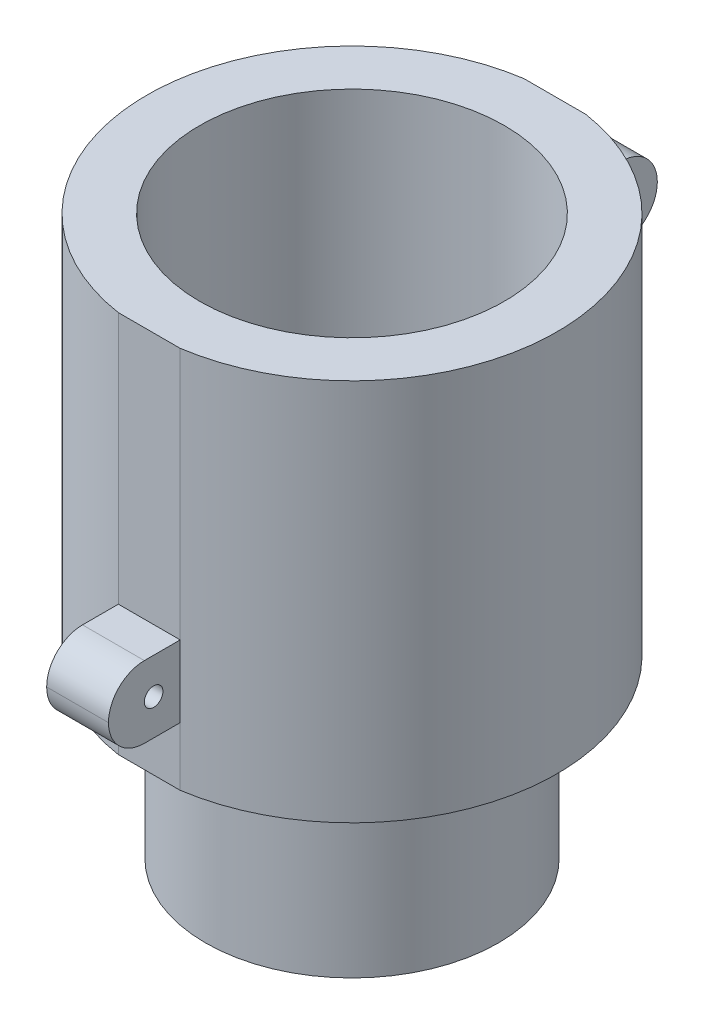
SolidWorks part; units mm, degrees
ref_plane "Front Plane" through (0, 0, 0) normal (0, 0, 1) x (1, 0, 0)
ref_plane "Top Plane" through (0, 0, 0) normal (0, 1, 0) x (1, 0, 0)
ref_plane "Right Plane" through (0, 0, 0) normal (1, 0, 0) x (0, 0, -1)
sketch "Sketch2" plane through (0, 0, 0) normal (0, 1, 0) x (1, 0, 0)
  circle A0 centre (0, 0) radius 17.5
  dimension "D1" = 35
extrude "Boss-Extrude1" add sketch "Sketch2" along normal blind 32.665
sketch "Sketch3" plane through (0, 0, 0) normal (0, -1, 0) x (1, 0, 0)
  circle A0 centre (0, 0) radius 12.5
extrude "Boss-Extrude2" add sketch "Sketch3" along normal blind 15
sketch "Sketch4" plane through (0, 32.665, 0) normal (0, 1, 0) x (1, 0, 0)
  circle A0 centre (0, 0) radius 13
extrude "Cut-Extrude1" cut sketch "Sketch4" against normal blind 25
sketch "Sketch8" plane through (0, 32.665, 0) normal (0, 1, 0) x (1, 0, 0)
  line L1 (-17.5, 0) -> (17.5, 0)
  line L2 (-17.5, 0) -> (-17.5, 17.3)
  line L3 (-17.5, 17.3) -> (17.5, 17.3)
  line L4 (17.5, 0) -> (17.5, 17.3)
  line L5 (-17.5, 0) -> (17.5, 0)
  line L6 (-17.5, 0) -> (-17.5, -17.3)
  line L7 (-17.5, -17.3) -> (17.5, -17.3)
  line L8 (17.5, 0) -> (17.5, -17.3)
  line L9 (-17.5, 17.3) -> (17.5, 17.3)
  line L10 (-17.5, 17.3) -> (-17.5, 19.0201)
  line L11 (-17.5, 19.0201) -> (17.5, 19.0201)
  line L12 (17.5, 17.3) -> (17.5, 19.0201)
  line L13 (-17.5, -17.3) -> (17.5, -17.3)
  line L14 (-17.5, -17.3) -> (-17.5, -19.1575)
  line L15 (-17.5, -19.1575) -> (17.5, -19.1575)
  line L16 (17.5, -17.3) -> (17.5, -19.1575)
  circle A0 centre (0, 0) radius 17.5 construction
extrude "Cut-Extrude4" cut sketch "Sketch8" against normal blind 35 contours L14 L13 L16 L15
sketch "Sketch11" plane through (0, 32.665, 0) normal (0, 1, 0) x (1, 0, 0)
  line L1 (-17.5, 0) -> (17.5, 0)
  line L2 (-17.5, 0) -> (-17.5, 17.3)
  line L3 (-17.5, 17.3) -> (17.5, 17.3)
  line L4 (17.5, 0) -> (17.5, 17.3)
  line L5 (-17.5, 17.3) -> (17.5, 17.3)
  line L6 (-17.5, 17.3) -> (-17.5, 19.5344)
  line L7 (-17.5, 19.5344) -> (17.5, 19.5344)
  line L8 (17.5, 17.3) -> (17.5, 19.5344)
  arc A0 (2.6382, -17.3) -> (-2.6382, -17.3) centre (0, 0) ccw construction
extrude "Cut-Extrude8" cut sketch "Sketch11" against normal blind 35 contours L6 L5 L8 L7
sketch "Sketch13" plane through (0, 0, -17.3) normal (0, 0, -1) x (-1, 0, 0)
  line L0 (-2.6382, 0) -> (-2.6382, 32.665) construction
  line L1 (-2.6382, 27.665) -> (2.6382, 27.665)
  line L2 (-2.6382, 27.665) -> (-2.6382, 21.5475)
  line L3 (-2.6382, 21.5475) -> (2.6382, 21.5475)
  line L4 (2.6382, 27.665) -> (2.6382, 21.5475)
  line L5 (2.6382, 32.665) -> (2.6382, 0) construction
  line L6 (2.6382, 32.665) -> (-2.6382, 32.665) construction
  dimension "D1" = 6.1175
  dimension "D2" = 5
extrude "Boss-Extrude3" add sketch "Sketch13" along normal blind 6.1175
sketch "Sketch14" plane through (0, 0, 17.3) normal (0, 0, 1) x (1, 0, 0)
  line L0 (-2.6382, 32.665) -> (-2.6382, 0) construction
  line L1 (-2.6382, 11.1175) -> (2.6382, 11.1175)
  line L2 (-2.6382, 11.1175) -> (-2.6382, 5)
  line L3 (-2.6382, 5) -> (2.6382, 5)
  line L4 (2.6382, 11.1175) -> (2.6382, 5)
  line L5 (2.6382, 0) -> (2.6382, 32.665) construction
  line L6 (-2.6382, 0) -> (2.6382, 0) construction
  dimension "D1" = 6.1175
  dimension "D2" = 5
extrude "Boss-Extrude4" add sketch "Sketch14" along normal blind 6.1175
sketch "Sketch15" plane through (2.6382, 0, 0) normal (1, 0, 0) x (0, 0, -1)
  line L0 (17.3, 27.665) -> (17.3, 21.5475) construction
  line L2 (23.4175, 27.665) -> (17.3, 27.665) construction
  circle A0 centre (19.565, 24.6062) radius 0.7937
  dimension "D1" = 2.265
  dimension "D2" = 3.0587
sketch "Sketch18" plane through (2.6382, 0, 0) normal (1, 0, 0) x (0, 0, -1)
  line L0 (-23.4175, 11.1175) -> (-17.3, 11.1175) construction
  line L1 (-17.3, 5) -> (-17.3, 11.1175) construction
  circle A0 centre (-19.565, 8.0575) radius 0.7937
  dimension "D1" = 3.06
  dimension "D2" = 2.265
extrude "Cut-Extrude11" cut sketch "Sketch18" against normal blind 6.1175 contours A0
extrude "Cut-Extrude12" cut sketch "Sketch15" against normal blind 6.1175 contours A0
fillet "Fillet8" radius 3.06 1 edges at (0, 27.665, -23.4175)
fillet "Fillet9" radius 3.06 1 edges at (0, 21.5475, -23.4175)
fillet "Fillet10" radius 3.06 1 edges at (0, 11.1175, 23.4175)
fillet "Fillet11" radius 3.06 1 edges at (0, 5, 23.4175)
